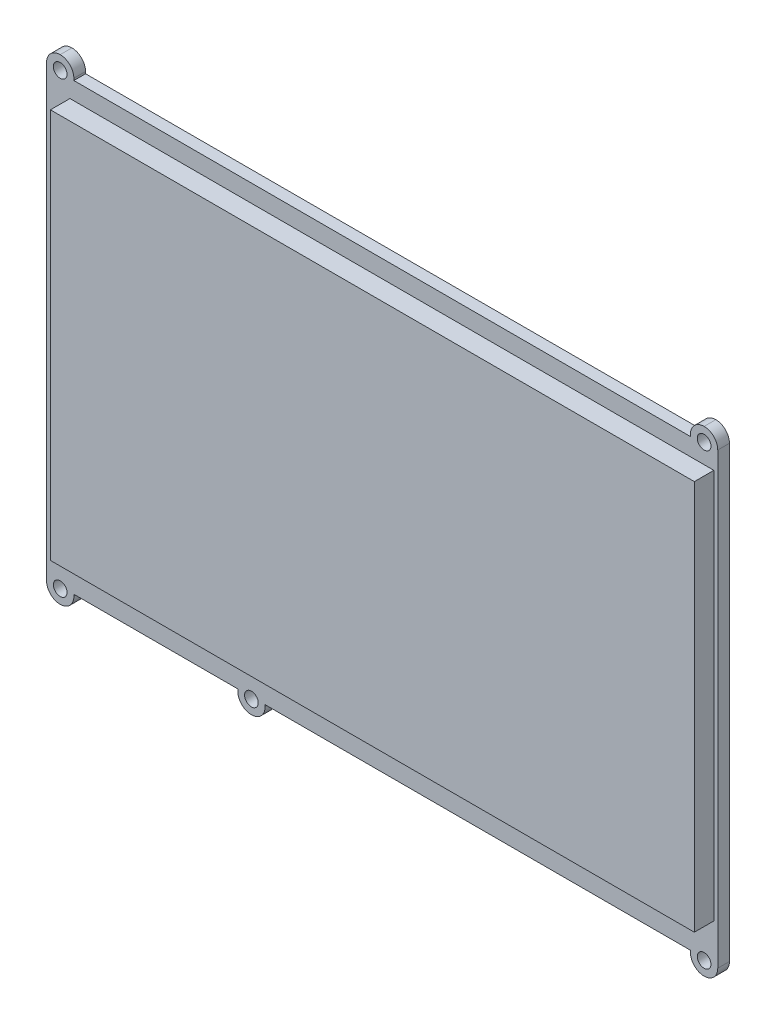
SolidWorks part; units mm, degrees
ref_plane "Front Plane" through (0, 0, 0) normal (0, 0, 1) x (1, 0, 0)
ref_plane "Top Plane" through (0, 0, 0) normal (0, 1, 0) x (1, 0, 0)
ref_plane "Right Plane" through (0, 0, 0) normal (1, 0, 0) x (0, 0, -1)
sketch "Sketch1" plane through (0, 0, 0) normal (0, 0, 1) x (1, 0, 0)
  line L0 (7, 122) -> (7, 118)
  line L1 (0, 0) -> (7, 0)
  line L2 (0, 0) -> (0, 122)
  line L3 (0, 122) -> (172, 122) construction
  line L4 (172, 0) -> (172, 122)
  line L5 (6, 113.5) -> (171, 113.5)
  line L6 (6, 113.5) -> (6, 13.5)
  line L7 (6, 13.5) -> (171, 13.5)
  line L8 (171, 113.5) -> (171, 13.5)
  line L9 (7, 118) -> (165, 118)
  line L10 (165, 118) -> (165, 122)
  line L11 (172, 122) -> (165, 122)
  line L12 (7, 122) -> (0, 122)
  line L14 (165, 0) -> (165, 4)
  line L15 (7, 0) -> (7, 4)
  line L16 (56, 4) -> (56, 0)
  line L17 (49, 4) -> (49, 0)
  line L18 (165, 0) -> (172, 0)
  line L21 (56, 4) -> (165, 4)
  line L22 (49, 0) -> (56, 0)
  line L23 (7, 4) -> (49, 4)
  circle A0 centre (3.5, 118.5) radius 1.75
  circle A1 centre (168.5, 118.5) radius 1.75
  circle A2 centre (168.5, 3.5) radius 1.75
  circle A3 centre (3.5, 3.5) radius 1.75
  circle A4 centre (52.5, 3.5) radius 1.75
  circle A5 centre (3.5, 61.5) radius 1.7428
  circle A6 centre (168.5, 61.5) radius 1.75 construction
  circle A7 centre (119.5, 61.5) radius 1.75 construction
  dimension "D7" = 3.5
  dimension "D8" = 3.5
  dimension "D9" = 2
  dimension "D10" = 2
  dimension "D13" = 165
  dimension "D15" = 115
  dimension "D16" = 4
  dimension "D21" = 49
  dimension "D24" = 3.5
  dimension "D1" = 172
  dimension "D2" = 3.5
  dimension "D3" = 165
  dimension "D4" = 100
  dimension "D5" = 1
  dimension "D6" = 58
  dimension "D11" = 2
  dimension "D12" = 3.5
  dimension "D14" = 49
  dimension "D17" = 7
  dimension "D18" = 7
  dimension "D19" = 3.5
  dimension "D20" = 3.5
  dimension "D22" = 58
  dimension "D23" = 3.5
extrude "Boss-Extrude1" add sketch "Sketch1" along normal blind 8 contours L6 L5 L8 L7
extrude "Boss-Extrude2" add sketch "Sketch1<4>" along normal blind 3
sketch "Sketch1<4>" plane through (0, 0, 0) normal (0, 0, 1) x (1, 0, 0) same geometry as "Sketch1"
fillet "Fillet3" radius 3.5 10 edges at (56, 0, 1.5) (165, 0, 1.5) (172, 0, 1.5) (49, 0, 1.5) (0, 0, 1.5) (7, 0, 1.5) (0, 122, 1.5) (7, 122, 1.5) (172, 122, 1.5) (165, 122, 1.5)
